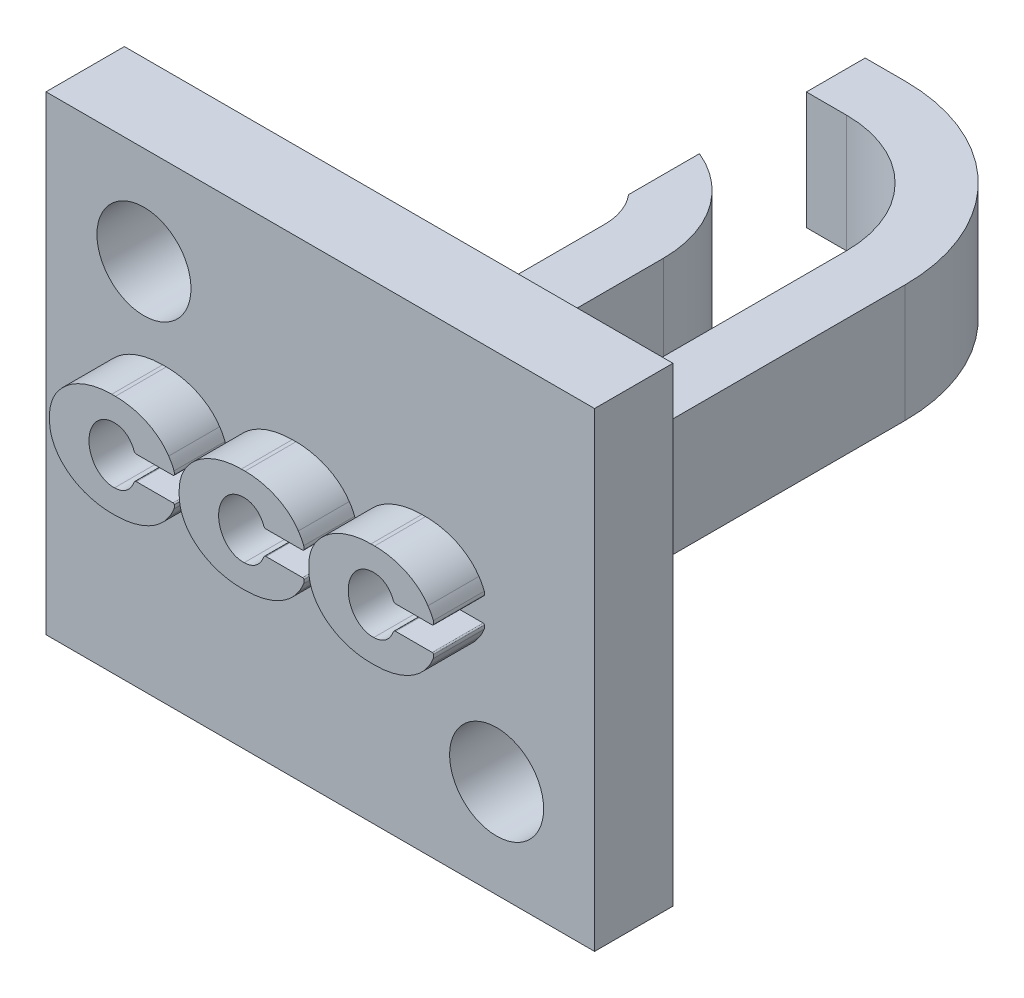
SolidWorks part; units mm, degrees
ref_plane "Front Plane" through (0, 0, 0) normal (0, 0, 1) x (1, 0, 0)
ref_plane "Top Plane" through (0, 0, 0) normal (0, 1, 0) x (1, 0, 0)
ref_plane "Right Plane" through (0, 0, 0) normal (1, 0, 0) x (0, 0, -1)
sketch "Sketch1" plane through (0, 0, 0) normal (0, 0, 1) x (1, 0, 0)
  line L1 (-7.5, 6) -> (7.5, 6)
  line L2 (-7.5, 6) -> (-7.5, -6)
  line L3 (-7.5, -6) -> (7.5, -6)
  line L4 (7.5, 6) -> (7.5, -6)
  line L5 (-7.5, 6) -> (7.5, -6) construction
  line L6 (-7.5, -6) -> (7.5, 6) construction
  point P0 (0, 0)
  dimension "D1" = 15
  dimension "D2" = 12
extrude "Boss-Extrude1" add sketch "Sketch1" along normal blind 2
sketch "Sketch2" plane through (0, 0, 2) normal (0, 0, 1) x (1, 0, 0)
  line L0 (-0.5835, 0.4438) -> (0.3524, 0.4438)
  line L1 (-1.1209, 1.4546) -> (-1.2145, 1.4546)
  line L2 (-2.8001, 0.2034) -> (-2.8001, 0.0733)
  line L3 (-1.2145, -1.1779) -> (-1.1209, -1.1779)
  line L4 (0.3478, -0.1633) -> (-0.5835, -0.1633)
  line L5 (-3.8918, 0.4438) -> (-2.956, 0.4438)
  line L6 (-4.4292, 1.4546) -> (-4.5228, 1.4546)
  line L7 (-6.1084, 0.2034) -> (-6.1084, 0.0733)
  line L8 (-4.5228, -1.1779) -> (-4.4292, -1.1779)
  line L9 (-2.9605, -0.1633) -> (-3.8918, -0.1633)
  line L10 (2.7248, 0.4438) -> (3.6607, 0.4438)
  line L11 (2.1874, 1.4546) -> (2.0938, 1.4546)
  line L12 (0.5082, 0.2034) -> (0.5082, 0.0733)
  line L13 (2.0938, -1.1779) -> (2.1874, -1.1779)
  line L14 (3.6561, -0.1633) -> (2.7248, -0.1633)
  arc A0 (-0.6452, 0.4874) -> (-0.5835, 0.4438) centre (-0.5835, 0.5092) ccw
  arc A1 (0.3524, 0.4438) -> (0.3816, 0.4686) centre (0.3479, 0.4787) ccw
  arc A2 (0.3816, 0.4686) -> (0.3774, 0.5561) centre (0.201, 0.5038) ccw
  arc A3 (0.3774, 0.5561) -> (0.2402, 0.8134) centre (-0.7046, 0.1445) ccw
  arc A4 (0.2402, -0.5368) -> (0.3727, -0.2904) centre (-0.6952, 0.1249) ccw
  arc A5 (0.3727, -0.2904) -> (0.3825, -0.1925) centre (0.2012, -0.2237) ccw
  arc A6 (0.3825, -0.1925) -> (0.3478, -0.1633) centre (0.3478, -0.1984) ccw
  arc A7 (-0.5835, -0.1633) -> (-0.6452, -0.2069) centre (-0.5835, -0.2287) ccw
  arc A8 (-3.9535, 0.4874) -> (-3.8918, 0.4438) centre (-3.8918, 0.5092) ccw
  arc A9 (-2.956, 0.4438) -> (-2.9267, 0.4686) centre (-2.9604, 0.4787) ccw
  arc A10 (-2.9267, 0.4686) -> (-2.9309, 0.5561) centre (-3.1073, 0.5038) ccw
  arc A11 (-2.9309, 0.5561) -> (-3.0681, 0.8134) centre (-4.0129, 0.1445) ccw
  arc A12 (-3.0681, -0.5368) -> (-2.9356, -0.2904) centre (-4.0035, 0.1249) ccw
  arc A13 (-2.9356, -0.2904) -> (-2.9258, -0.1925) centre (-3.1071, -0.2237) ccw
  arc A14 (-2.9258, -0.1925) -> (-2.9605, -0.1633) centre (-2.9605, -0.1984) ccw
  arc A15 (-3.8918, -0.1633) -> (-3.9535, -0.2069) centre (-3.8918, -0.2287) ccw
  arc A16 (2.6631, 0.4874) -> (2.7248, 0.4438) centre (2.7248, 0.5092) ccw
  arc A17 (3.6607, 0.4438) -> (3.6899, 0.4686) centre (3.6562, 0.4787) ccw
  arc A18 (3.6899, 0.4686) -> (3.6857, 0.5561) centre (3.5093, 0.5038) ccw
  arc A19 (3.6857, 0.5561) -> (3.5485, 0.8134) centre (2.6037, 0.1445) ccw
  arc A20 (3.5485, -0.5368) -> (3.681, -0.2904) centre (2.6131, 0.1249) ccw
  arc A21 (3.681, -0.2904) -> (3.6908, -0.1925) centre (3.5095, -0.2237) ccw
  arc A22 (3.6908, -0.1925) -> (3.6561, -0.1633) centre (3.6561, -0.1984) ccw
  arc A23 (2.7248, -0.1633) -> (2.6631, -0.2069) centre (2.7248, -0.2287) ccw
  ellipse E0 centre (-1.1734, 0.1385) end of major axis (-1.177, 0.8556) minor radius 0.6209 (-1.2015, 0.8549) -> (-1.1417, -0.5777) ccw
  ellipse E1 centre (-1.2295, 0.1385) end of major axis (-1.5121, -0.5431) minor radius 0.6039 (-0.6452, 0.4874) -> (-1.2015, 0.8549) ccw
  ellipse E2 centre (-1.2429, 0.1529) end of major axis (-2.8857, -0.0922) minor radius 1.2925 (0.2402, 0.8134) -> (-1.1209, 1.4546) ccw
  ellipse E3 centre (-1.1521, 0.1542) end of major axis (0.4928, 0.0248) minor radius 1.2979 (-1.2145, 1.4546) -> (-2.8001, 0.2034) ccw
  ellipse E4 centre (-1.1521, 0.1225) end of major axis (0.4928, 0.2518) minor radius 1.2979 (-2.8001, 0.0733) -> (-1.2145, -1.1779) ccw
  ellipse E5 centre (-1.2429, 0.1238) end of major axis (-2.8857, 0.3689) minor radius 1.2925 (-1.1209, -1.1779) -> (0.2402, -0.5368) ccw
  ellipse E6 centre (-1.2295, 0.1421) end of major axis (-0.9469, -0.5396) minor radius 0.6039 (-1.1417, -0.5777) -> (-0.6452, -0.2069) ccw
  ellipse E7 centre (-4.5378, 0.1385) end of major axis (-4.8204, -0.5431) minor radius 0.6039 (-3.9535, 0.4874) -> (-4.5098, 0.8549) ccw
  ellipse E8 centre (-4.5512, 0.1529) end of major axis (-6.194, -0.0922) minor radius 1.2925 (-3.0681, 0.8134) -> (-4.4292, 1.4546) ccw
  ellipse E9 centre (-4.4604, 0.1542) end of major axis (-6.1053, 0.2835) minor radius 1.2979 (-4.5228, 1.4546) -> (-6.1084, 0.2034) ccw
  ellipse E10 centre (-4.4604, 0.1225) end of major axis (-6.1053, -0.0069) minor radius 1.2979 (-6.1084, 0.0733) -> (-4.5228, -1.1779) ccw
  ellipse E11 centre (-4.5512, 0.1238) end of major axis (-6.194, 0.3689) minor radius 1.2925 (-4.4292, -1.1779) -> (-3.0681, -0.5368) ccw
  ellipse E12 centre (-4.5378, 0.1421) end of major axis (-4.2552, -0.5396) minor radius 0.6039 (-4.45, -0.5777) -> (-3.9535, -0.2069) ccw
  ellipse E13 centre (-4.4817, 0.1385) end of major axis (-4.4853, 0.8556) minor radius 0.6209 (-4.5098, 0.8549) -> (-4.45, -0.5777) ccw
  ellipse E14 centre (2.1349, 0.1385) end of major axis (2.1385, -0.5786) minor radius 0.6209 (2.1069, 0.8549) -> (2.1666, -0.5777) ccw
  ellipse E15 centre (2.0788, 0.1385) end of major axis (2.3614, 0.8201) minor radius 0.6039 (2.6631, 0.4874) -> (2.1069, 0.8549) ccw
  ellipse E16 centre (2.0654, 0.1529) end of major axis (3.7082, 0.3981) minor radius 1.2925 (3.5485, 0.8134) -> (2.1874, 1.4546) ccw
  ellipse E17 centre (2.1562, 0.1542) end of major axis (0.5113, 0.2835) minor radius 1.2979 (2.0938, 1.4546) -> (0.5082, 0.2034) ccw
  ellipse E18 centre (2.1562, 0.1225) end of major axis (3.8011, 0.2518) minor radius 1.2979 (0.5082, 0.0733) -> (2.0938, -1.1779) ccw
  ellipse E19 centre (2.0654, 0.1238) end of major axis (0.4226, 0.3689) minor radius 1.2925 (2.1874, -1.1779) -> (3.5485, -0.5368) ccw
  ellipse E20 centre (2.0788, 0.1421) end of major axis (2.3614, -0.5396) minor radius 0.6039 (2.1666, -0.5777) -> (2.6631, -0.2069) ccw
extrude "Boss-Extrude2" add sketch "Sketch2" along normal blind 2
sketch "Sketch3" plane through (0, 0, 0) normal (0, 1, 0) x (1, 0, 0)
  line L0 (7.5, 0) -> (-7.5, 0) construction
  line L1 (1.7287, 0) -> (3.2287, 0)
  line L2 (1.7287, 0) -> (1.7287, 12.2)
  line L3 (-3.644, -2) -> (-3.644, 5.3789) construction
  line L4 (3.2287, 0) -> (3.2287, 13.7)
  line L5 (-4.394, 0) -> (-2.894, 0)
  line L6 (-4.394, 0) -> (-4.394, 3.5)
  line L7 (-1.1926, -2) -> (-1.1926, 4.6797) construction
  line L8 (-2.894, 0) -> (-2.894, 3.5)
  line L9 (-2.894, 3.5) -> (-4.394, 3.5)
  line L10 (-1.9426, 0) -> (-0.4426, 0)
  line L13 (-1.9426, 0) -> (-1.9426, 8.2)
  line L14 (2.4787, -2) -> (2.4787, 2.787) construction
  line L15 (-0.4426, 0) -> (-0.4426, 9.7)
  line L16 (-0.4426, 9.7) -> (-3.4426, 9.7)
  line L17 (-3.4426, 13.7) -> (3.2287, 13.7)
  line L18 (-1.9426, 8.2) -> (-3.4426, 8.2)
  line L19 (-3.4426, 9.7) -> (-3.4426, 8.2)
  line L20 (-3.4426, 13.7) -> (-3.4426, 12.2)
  line L21 (-3.4426, 12.2) -> (1.7287, 12.2)
  dimension "D1" = 1.5
  dimension "D2" = 3.5
  dimension "D3" = 1.5
  dimension "D4" = 1.5
  dimension "D5" = 8.2
  dimension "D6" = 1.5
  dimension "D7" = 2.5
  dimension "D8" = 1.5
  dimension "D9" = 1.5
  dimension "D10" = 3.644
  dimension "D11" = 1.1926
  dimension "D12" = 2.4787
extrude "Boss-Extrude3" add sketch "Sketch3" along normal mid plane 3
fillet "Fillet3" radius 1.5 1 edges at (-1.9426, 0, -8.2)
fillet "Fillet4" radius 3 1 edges at (-0.4426, 0, -9.7)
fillet "Fillet5" radius 3 1 edges at (1.7287, 0, -12.2)
fillet "Fillet6" radius 4.5 1 edges at (3.2287, 0, -13.7)
sketch "Sketch4" plane through (7.5, 0, 0) normal (1, 0, 0) x (0, 0, -1)
  line L4 (0, -6) -> (0, 6)
  line L5 (0, 6) -> (-2, 6)
  line L6 (-2, 6) -> (-2, -6)
  line L7 (-2, -6) -> (0, -6)
  line L8 (0, -6) -> (0, 6)
  line L9 (0, 6) -> (-2, 6)
  line L10 (-2, 6) -> (-2, -6)
  line L11 (-2, -6) -> (0, -6)
  dimension "D1" = 0
extrude "Cut-Extrude1" cut sketch "Sketch4" against normal blind 1
sketch "Sketch5" plane through (0, 0, 0) normal (0, 0, -1) x (-1, 0, 0)
  line L0 (-6.5, -6) -> (-6.5, 6) construction
  line L1 (7.5, -6) -> (-6.5, -6) construction
  line L2 (7.5, 6) -> (7.5, -6) construction
  line L3 (-6.5, 6) -> (7.5, 6) construction
  circle A0 centre (-4, -3.5) radius 1.2
  circle A1 centre (5, 3.5) radius 1.2
  dimension "D1" = 2.4
  dimension "D2" = 2.5
  dimension "D3" = 2.5
  dimension "D4" = 2.5
  dimension "D5" = 2.5
extrude "Cut-Extrude2" cut sketch "Sketch5" against normal through all
sketch "Sketch6" plane through (0, 0, 4) normal (0, 0, 1) x (1, 0, 0)
  line L0 (2.7248, 0.4438) -> (3.6607, 0.4438) construction
  line L1 (2.1874, 1.4546) -> (2.0938, 1.4546) construction
  line L2 (0.5082, 0.2034) -> (0.5082, 0.0733) construction
  line L3 (2.0938, -1.1779) -> (2.1874, -1.1779) construction
  line L4 (3.6561, -0.1633) -> (2.7248, -0.1633) construction
  line L5 (-0.5835, 0.4438) -> (0.3524, 0.4438) construction
  line L6 (-1.1209, 1.4546) -> (-1.2145, 1.4546) construction
  line L7 (-2.8001, 0.2034) -> (-2.8001, 0.0733) construction
  line L8 (-1.2145, -1.1779) -> (-1.1209, -1.1779) construction
  line L9 (0.3478, -0.1633) -> (-0.5835, -0.1633) construction
  line L10 (-3.8918, 0.4438) -> (-2.956, 0.4438) construction
  line L11 (-4.4292, 1.4546) -> (-4.5228, 1.4546) construction
  line L12 (-6.1084, 0.2034) -> (-6.1084, 0.0733) construction
  line L13 (-4.5228, -1.1779) -> (-4.4292, -1.1779) construction
  line L14 (-2.9605, -0.1633) -> (-3.8918, -0.1633) construction
  line L15 (2.7248, 0.4438) -> (3.6607, 0.4438)
  line L16 (2.1874, 1.4546) -> (2.0938, 1.4546)
  line L17 (0.5082, 0.2034) -> (0.5082, 0.0733)
  line L18 (2.0938, -1.1779) -> (2.1874, -1.1779)
  line L19 (3.6561, -0.1633) -> (2.7248, -0.1633)
  line L20 (-0.5835, 0.4438) -> (0.3524, 0.4438)
  line L21 (-1.1209, 1.4546) -> (-1.2145, 1.4546)
  line L22 (-2.8001, 0.2034) -> (-2.8001, 0.0733)
  line L23 (-1.2145, -1.1779) -> (-1.1209, -1.1779)
  line L24 (0.3478, -0.1633) -> (-0.5835, -0.1633)
  line L25 (-3.8918, 0.4438) -> (-2.956, 0.4438)
  line L26 (-4.4292, 1.4546) -> (-4.5228, 1.4546)
  line L27 (-6.1084, 0.2034) -> (-6.1084, 0.0733)
  line L28 (-4.5228, -1.1779) -> (-4.4292, -1.1779)
  line L29 (-2.9605, -0.1633) -> (-3.8918, -0.1633)
  arc A0 (2.6631, 0.4874) -> (2.7248, 0.4438) centre (2.7248, 0.5092) ccw construction
  arc A1 (3.6607, 0.4438) -> (3.6899, 0.4686) centre (3.6562, 0.4787) ccw construction
  arc A2 (3.6899, 0.4686) -> (3.6857, 0.5561) centre (3.5093, 0.5038) ccw construction
  arc A3 (3.6857, 0.5561) -> (3.5485, 0.8134) centre (2.6037, 0.1445) ccw construction
  arc A4 (3.5485, -0.5368) -> (3.681, -0.2904) centre (2.6131, 0.1249) ccw construction
  arc A5 (3.681, -0.2904) -> (3.6908, -0.1925) centre (3.5095, -0.2237) ccw construction
  arc A6 (3.6908, -0.1925) -> (3.6561, -0.1633) centre (3.6561, -0.1984) ccw construction
  arc A7 (2.7248, -0.1633) -> (2.6631, -0.2069) centre (2.7248, -0.2287) ccw construction
  arc A8 (-0.6452, 0.4874) -> (-0.5835, 0.4438) centre (-0.5835, 0.5092) ccw construction
  arc A9 (0.3524, 0.4438) -> (0.3816, 0.4686) centre (0.3479, 0.4787) ccw construction
  arc A10 (0.3816, 0.4686) -> (0.3774, 0.5561) centre (0.201, 0.5038) ccw construction
  arc A11 (0.3774, 0.5561) -> (0.2402, 0.8134) centre (-0.7046, 0.1445) ccw construction
  arc A12 (0.2402, -0.5368) -> (0.3727, -0.2904) centre (-0.6952, 0.1249) ccw construction
  arc A13 (0.3727, -0.2904) -> (0.3825, -0.1925) centre (0.2012, -0.2237) ccw construction
  arc A14 (0.3825, -0.1925) -> (0.3478, -0.1633) centre (0.3478, -0.1984) ccw construction
  arc A15 (-0.5835, -0.1633) -> (-0.6452, -0.2069) centre (-0.5835, -0.2287) ccw construction
  arc A16 (-3.9535, 0.4874) -> (-3.8918, 0.4438) centre (-3.8918, 0.5092) ccw construction
  arc A17 (-2.956, 0.4438) -> (-2.9267, 0.4686) centre (-2.9604, 0.4787) ccw construction
  arc A18 (-2.9267, 0.4686) -> (-2.9309, 0.5561) centre (-3.1073, 0.5038) ccw construction
  arc A19 (-2.9309, 0.5561) -> (-3.0681, 0.8134) centre (-4.0129, 0.1445) ccw construction
  arc A20 (-3.0681, -0.5368) -> (-2.9356, -0.2904) centre (-4.0035, 0.1249) ccw construction
  arc A21 (-2.9356, -0.2904) -> (-2.9258, -0.1925) centre (-3.1071, -0.2237) ccw construction
  arc A22 (-2.9258, -0.1925) -> (-2.9605, -0.1633) centre (-2.9605, -0.1984) ccw construction
  arc A23 (-3.8918, -0.1633) -> (-3.9535, -0.2069) centre (-3.8918, -0.2287) ccw construction
  arc A24 (2.6631, 0.4874) -> (2.7248, 0.4438) centre (2.7248, 0.5092) ccw
  arc A25 (3.6607, 0.4438) -> (3.6899, 0.4686) centre (3.6562, 0.4787) ccw
  arc A26 (3.6899, 0.4686) -> (3.6857, 0.5561) centre (3.5093, 0.5038) ccw
  arc A27 (3.6857, 0.5561) -> (3.5485, 0.8134) centre (2.6037, 0.1445) ccw
  arc A28 (3.5485, -0.5368) -> (3.681, -0.2904) centre (2.6131, 0.1249) ccw
  arc A29 (3.681, -0.2904) -> (3.6908, -0.1925) centre (3.5095, -0.2237) ccw
  arc A30 (3.6908, -0.1925) -> (3.6561, -0.1633) centre (3.6561, -0.1984) ccw
  arc A31 (2.7248, -0.1633) -> (2.6631, -0.2069) centre (2.7248, -0.2287) ccw
  arc A32 (-0.6452, 0.4874) -> (-0.5835, 0.4438) centre (-0.5835, 0.5092) ccw
  arc A33 (0.3524, 0.4438) -> (0.3816, 0.4686) centre (0.3479, 0.4787) ccw
  arc A34 (0.3816, 0.4686) -> (0.3774, 0.5561) centre (0.201, 0.5038) ccw
  arc A35 (0.3774, 0.5561) -> (0.2402, 0.8134) centre (-0.7046, 0.1445) ccw
  arc A36 (0.2402, -0.5368) -> (0.3727, -0.2904) centre (-0.6952, 0.1249) ccw
  arc A37 (0.3727, -0.2904) -> (0.3825, -0.1925) centre (0.2012, -0.2237) ccw
  arc A38 (0.3825, -0.1925) -> (0.3478, -0.1633) centre (0.3478, -0.1984) ccw
  arc A39 (-0.5835, -0.1633) -> (-0.6452, -0.2069) centre (-0.5835, -0.2287) ccw
  arc A40 (-3.9535, 0.4874) -> (-3.8918, 0.4438) centre (-3.8918, 0.5092) ccw
  arc A41 (-2.956, 0.4438) -> (-2.9267, 0.4686) centre (-2.9604, 0.4787) ccw
  arc A42 (-2.9267, 0.4686) -> (-2.9309, 0.5561) centre (-3.1073, 0.5038) ccw
  arc A43 (-2.9309, 0.5561) -> (-3.0681, 0.8134) centre (-4.0129, 0.1445) ccw
  arc A44 (-3.0681, -0.5368) -> (-2.9356, -0.2904) centre (-4.0035, 0.1249) ccw
  arc A45 (-2.9356, -0.2904) -> (-2.9258, -0.1925) centre (-3.1071, -0.2237) ccw
  arc A46 (-2.9258, -0.1925) -> (-2.9605, -0.1633) centre (-2.9605, -0.1984) ccw
  arc A47 (-3.8918, -0.1633) -> (-3.9535, -0.2069) centre (-3.8918, -0.2287) ccw
  ellipse E0 centre (2.0788, 0.1385) end of major axis (1.7962, -0.5431) minor radius 0.6039 (2.6631, 0.4874) -> (2.1069, 0.8549) ccw construction
  ellipse E1 centre (2.0654, 0.1529) end of major axis (0.4226, -0.0922) minor radius 1.2925 (3.5485, 0.8134) -> (2.1874, 1.4546) ccw construction
  ellipse E2 centre (2.1562, 0.1542) end of major axis (0.5113, 0.2835) minor radius 1.2979 (2.0938, 1.4546) -> (0.5082, 0.2034) ccw construction
  ellipse E3 centre (2.1562, 0.1225) end of major axis (3.8011, 0.2518) minor radius 1.2979 (0.5082, 0.0733) -> (2.0938, -1.1779) ccw construction
  ellipse E4 centre (2.0654, 0.1238) end of major axis (0.4226, 0.3689) minor radius 1.2925 (2.1874, -1.1779) -> (3.5485, -0.5368) ccw construction
  ellipse E5 centre (2.0788, 0.1421) end of major axis (2.3614, -0.5396) minor radius 0.6039 (2.1666, -0.5777) -> (2.6631, -0.2069) ccw construction
  ellipse E6 centre (2.1349, 0.1385) end of major axis (2.1385, -0.5786) minor radius 0.6209 (2.1069, 0.8549) -> (2.1666, -0.5777) ccw construction
  ellipse E7 centre (-1.2295, 0.1385) end of major axis (-1.5121, -0.5431) minor radius 0.6039 (-0.6452, 0.4874) -> (-1.2015, 0.8549) ccw construction
  ellipse E8 centre (-1.2429, 0.1529) end of major axis (0.3999, 0.3981) minor radius 1.2925 (0.2402, 0.8134) -> (-1.1209, 1.4546) ccw construction
  ellipse E9 centre (-1.1521, 0.1542) end of major axis (-2.797, 0.2835) minor radius 1.2979 (-1.2145, 1.4546) -> (-2.8001, 0.2034) ccw construction
  ellipse E10 centre (-1.1521, 0.1225) end of major axis (0.4928, 0.2518) minor radius 1.2979 (-2.8001, 0.0733) -> (-1.2145, -1.1779) ccw construction
  ellipse E11 centre (-1.2429, 0.1238) end of major axis (0.3999, -0.1214) minor radius 1.2925 (-1.1209, -1.1779) -> (0.2402, -0.5368) ccw construction
  ellipse E12 centre (-1.2295, 0.1421) end of major axis (-0.9469, -0.5396) minor radius 0.6039 (-1.1417, -0.5777) -> (-0.6452, -0.2069) ccw construction
  ellipse E13 centre (-1.1734, 0.1385) end of major axis (-1.1698, -0.5786) minor radius 0.6209 (-1.2015, 0.8549) -> (-1.1417, -0.5777) ccw construction
  ellipse E14 centre (-4.5378, 0.1385) end of major axis (-4.8204, -0.5431) minor radius 0.6039 (-3.9535, 0.4874) -> (-4.5098, 0.8549) ccw construction
  ellipse E15 centre (-4.5512, 0.1529) end of major axis (-2.9084, 0.3981) minor radius 1.2925 (-3.0681, 0.8134) -> (-4.4292, 1.4546) ccw construction
  ellipse E16 centre (-4.4604, 0.1542) end of major axis (-6.1053, 0.2835) minor radius 1.2979 (-4.5228, 1.4546) -> (-6.1084, 0.2034) ccw construction
  ellipse E17 centre (-4.4604, 0.1225) end of major axis (-2.8155, 0.2518) minor radius 1.2979 (-6.1084, 0.0733) -> (-4.5228, -1.1779) ccw construction
  ellipse E18 centre (-4.5512, 0.1238) end of major axis (-6.194, 0.3689) minor radius 1.2925 (-4.4292, -1.1779) -> (-3.0681, -0.5368) ccw construction
  ellipse E19 centre (-4.5378, 0.1421) end of major axis (-4.2552, -0.5396) minor radius 0.6039 (-4.45, -0.5777) -> (-3.9535, -0.2069) ccw construction
  ellipse E20 centre (-4.4817, 0.1385) end of major axis (-4.4781, -0.5786) minor radius 0.6209 (-4.5098, 0.8549) -> (-4.45, -0.5777) ccw construction
  ellipse E21 centre (2.0788, 0.1385) end of major axis (1.7962, -0.5431) minor radius 0.6039 (2.6631, 0.4874) -> (2.1069, 0.8549) ccw
  ellipse E22 centre (2.0654, 0.1529) end of major axis (3.7082, 0.3981) minor radius 1.2925 (3.5485, 0.8134) -> (2.1874, 1.4546) ccw
  ellipse E23 centre (2.1562, 0.1542) end of major axis (0.5113, 0.2835) minor radius 1.2979 (2.0938, 1.4546) -> (0.5082, 0.2034) ccw
  ellipse E24 centre (2.1562, 0.1225) end of major axis (3.8011, 0.2518) minor radius 1.2979 (0.5082, 0.0733) -> (2.0938, -1.1779) ccw
  ellipse E25 centre (2.0654, 0.1238) end of major axis (0.4226, 0.3689) minor radius 1.2925 (2.1874, -1.1779) -> (3.5485, -0.5368) ccw
  ellipse E26 centre (2.0788, 0.1421) end of major axis (2.3614, -0.5396) minor radius 0.6039 (2.1666, -0.5777) -> (2.6631, -0.2069) ccw
  ellipse E27 centre (2.1349, 0.1385) end of major axis (2.1385, -0.5786) minor radius 0.6209 (2.1069, 0.8549) -> (2.1666, -0.5777) ccw
  ellipse E28 centre (-1.2295, 0.1385) end of major axis (-1.5121, -0.5431) minor radius 0.6039 (-0.6452, 0.4874) -> (-1.2015, 0.8549) ccw
  ellipse E29 centre (-1.2429, 0.1529) end of major axis (0.3999, 0.3981) minor radius 1.2925 (0.2402, 0.8134) -> (-1.1209, 1.4546) ccw
  ellipse E30 centre (-1.1521, 0.1542) end of major axis (-2.797, 0.2835) minor radius 1.2979 (-1.2145, 1.4546) -> (-2.8001, 0.2034) ccw
  ellipse E31 centre (-1.1521, 0.1225) end of major axis (0.4928, 0.2518) minor radius 1.2979 (-2.8001, 0.0733) -> (-1.2145, -1.1779) ccw
  ellipse E32 centre (-1.2429, 0.1238) end of major axis (-2.8857, 0.3689) minor radius 1.2925 (-1.1209, -1.1779) -> (0.2402, -0.5368) ccw
  ellipse E33 centre (-1.2295, 0.1421) end of major axis (-0.9469, -0.5396) minor radius 0.6039 (-1.1417, -0.5777) -> (-0.6452, -0.2069) ccw
  ellipse E34 centre (-1.1734, 0.1385) end of major axis (-1.1698, -0.5786) minor radius 0.6209 (-1.2015, 0.8549) -> (-1.1417, -0.5777) ccw
  ellipse E35 centre (-4.5378, 0.1385) end of major axis (-4.8204, -0.5431) minor radius 0.6039 (-3.9535, 0.4874) -> (-4.5098, 0.8549) ccw
  ellipse E36 centre (-4.5512, 0.1529) end of major axis (-2.9084, 0.3981) minor radius 1.2925 (-3.0681, 0.8134) -> (-4.4292, 1.4546) ccw
  ellipse E37 centre (-4.4604, 0.1542) end of major axis (-6.1053, 0.2835) minor radius 1.2979 (-4.5228, 1.4546) -> (-6.1084, 0.2034) ccw
  ellipse E38 centre (-4.4604, 0.1225) end of major axis (-2.8155, 0.2518) minor radius 1.2979 (-6.1084, 0.0733) -> (-4.5228, -1.1779) ccw
  ellipse E39 centre (-4.5512, 0.1238) end of major axis (-6.194, 0.3689) minor radius 1.2925 (-4.4292, -1.1779) -> (-3.0681, -0.5368) ccw
  ellipse E40 centre (-4.5378, 0.1421) end of major axis (-4.2552, -0.5396) minor radius 0.6039 (-4.45, -0.5777) -> (-3.9535, -0.2069) ccw
  ellipse E41 centre (-4.4817, 0.1385) end of major axis (-4.4781, -0.5786) minor radius 0.6209 (-4.5098, 0.8549) -> (-4.45, -0.5777) ccw
extrude "Cut-Extrude3" cut sketch "Sketch6" against normal blind 0.7
sketch "Sketch7" plane through (0, 1.5, 0) normal (0, 1, 0) x (1, 0, 0)
  line L0 (-1.2713, 13.7) -> (-3.4426, 13.7) construction
  line L1 (-3.4426, 13.7) -> (-2.294, 13.7)
  line L2 (-3.4426, 13.7) -> (-3.4426, 7.5)
  line L3 (-3.4426, 7.5) -> (-2.294, 7.5)
  line L4 (-2.294, 13.7) -> (-2.294, 7.5)
  line L5 (-2.594, 7.5) -> (-2.594, 10.2) construction
  line L6 (-3.4426, 13.7) -> (-3.4426, 12.2) construction
  dimension "D1" = 0.3
extrude "Cut-Extrude4" cut sketch "Sketch7" against normal through all
sketch "Sketch8" plane through (0, 1.5, 0) normal (0, 1, 0) x (1, 0, 0)
  line L0 (6.5, 0) -> (-7.5, 0) construction
  line L1 (-4.394, 3.5) -> (-4.194, 3.5)
  line L2 (-4.394, 3.5) -> (-4.394, 0)
  line L3 (-4.394, 0) -> (-4.194, 0)
  line L4 (-4.194, 3.5) -> (-4.194, 0)
  dimension "D1" = 0.2
extrude "Cut-Extrude5" cut sketch "Sketch8" against normal through all
